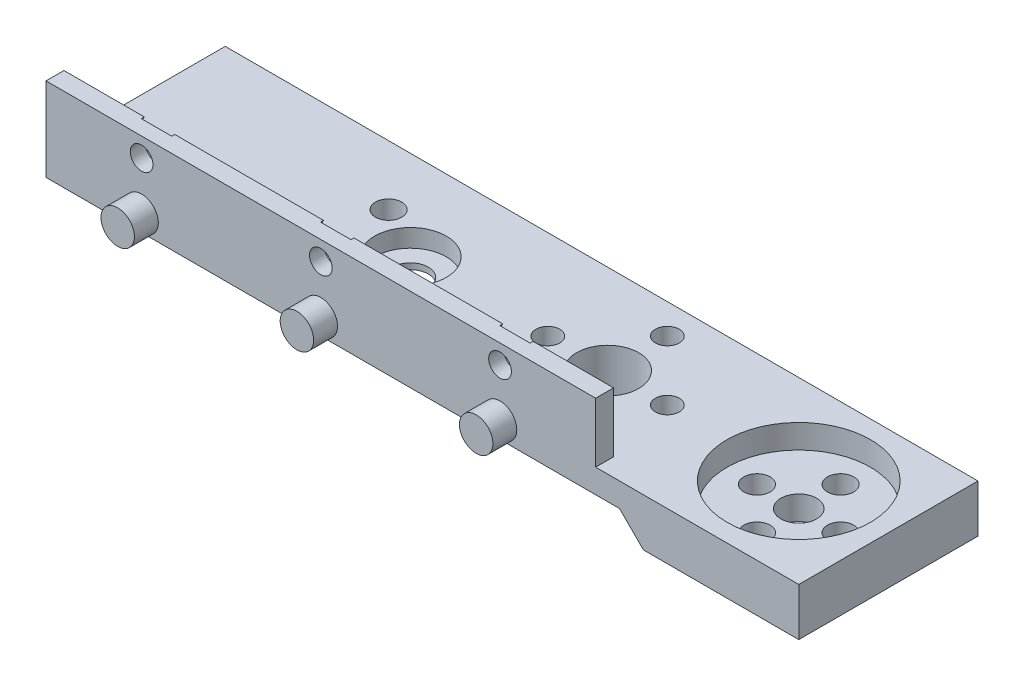
SolidWorks part; units mm, degrees
note: The reader was unsure of these and kept them because the rebuilt part matched: shared geometry of "草图2<3>", "草图1<3>", "草图1<4>", "草图1<5>", "草图1<6>".
ref_plane "前视基准面" through (0, 0, 0) normal (0, 0, 1) x (1, 0, 0)
ref_plane "上视基准面" through (0, 0, 0) normal (0, 1, 0) x (1, 0, 0)
ref_plane "右视基准面" through (0, 0, 0) normal (1, 0, 0) x (0, 0, -1)
other "Configuration Table"
sketch "草图1" plane through (0, 0, 0) normal (0, 1, 0) x (1, 0, 0)
  line L0 (-31.5, 7.5) -> (31.5, 7.5)
  line L1 (31.5, 7.5) -> (31.5, -7.5)
  line L2 (31.5, -7.5) -> (-31.5, -7.5)
  line L3 (-31.5, -7.5) -> (-31.5, 7.5)
  line L4 (-31.5, 0) -> (31.5, 0) construction
  line L5 (-12.8301, -2.5) -> (-4.1699, 2.5) construction
  line L6 (-13.3083, -5.95) -> (-3.6917, -5.95) construction
  line L7 (-13.3083, 5.95) -> (-3.6917, 5.95) construction
  line L8 (-8.5, 7.5) -> (-8.5, -7.5) construction
  line L9 (8, 0) -> (8, 4.5778) construction
  line L11 (31.5, 7.5) -> (16.5, 7.5)
  line L12 (31.5, 7.5) -> (31.5, -7.5)
  line L13 (31.5, -7.5) -> (16.5, -7.5)
  line L14 (16.5, 7.5) -> (16.5, -7.5)
  circle A0 centre (-8.5, 0) radius 1.5
  circle A1 centre (-4.1699, 2.5) radius 1.1
  circle A3 centre (-12.8301, -2.5) radius 1.1
  arc A4 (-13.3083, 5.95) -> (-13.3083, -5.95) centre (-8.5, 0) ccw construction
  circle A5 centre (8, 0) radius 2.6
  arc A6 (-3.6917, -5.95) -> (-3.6917, 5.95) centre (-8.5, 0) ccw construction
  circle A7 centre (24, 0) radius 1.5
  circle A8 centre (24, 0) radius 3.5 construction
  circle A9 centre (27.5, 0) radius 1.1
  circle A10 centre (24, -3.5) radius 1.1
  circle A11 centre (20.5, 0) radius 1.1
  circle A12 centre (24, 3.5) radius 1.1
  circle A13 centre (-12.8301, 2.5) radius 1.1
  circle A14 centre (-4.1699, -2.5) radius 1.1
  circle A15 centre (13, 0) radius 1
  circle A18 centre (3, 0) radius 1
  circle A19 centre (8, 5) radius 1
  circle A20 centre (8, -5) radius 1 [skipped]
  circle A21 centre (24, 0) radius 6
  circle A22 centre (8, 0) radius 4
  point P5 (0, 7.5)
  point P7 (-31.5, 0)
  dimension "D3" = 3
  dimension "D6" = 2.2
  dimension "D9" = 15.3
  dimension "D12" = 5.2
  dimension "D14" = 3
  dimension "D15" = 7
  dimension "D16" = 2.2
  dimension "D18" = 2
  dimension "D22" = 12
  dimension "D1" = 63
  dimension "D2" = 15
  dimension "D4" = 23
  dimension "D7" = 30
  dimension "D8" = 10
  dimension "D10" = 11.9
  dimension "D11" = 16.5
  dimension "D13" = 16
  dimension "D19" = 5
  dimension "D21" = 15
  dimension "D5" = 2
  dimension "D17" = 4
  dimension "D20" = 4
extrude "凸台-拉伸1" add sketch "草图1" along normal blind 2 contours A3 | L14 L0 L3 L2 A22 A15 A18 A19 A13 A3 A1 A0 A14 | L0 L14 L2 L1 A21 | A21 A7 A9 A10 A11 A12 | A22 A5 | A1
sketch "草图2" plane through (0, 0, 7.5) normal (0, 0, 1) x (1, 0, 0)
  line L0 (-31, 1.4) -> (31, 1.4) construction
  line L1 (-31.5, 2) -> (-31.5, 0) construction
  line L3 (31.5, 0) -> (-31.5, 0) construction
  circle A0 centre (-23.5, 1.4) radius 1.4
  circle A1 centre (-8.5, 1.4) radius 1.4
  circle A2 centre (6.5, 1.4) radius 1.4
  circle A3 centre (-23.5, 5.4) radius 0.95
  circle A4 centre (-8.5, 5.4) radius 0.95
  circle A5 centre (6.5, 5.4) radius 0.95
  line M10 (31.5, 2) -> (-31.5, 2)
  dimension "D1" = 2.8
  dimension "D2" = 2.8
  dimension "D3" = 2.8
  dimension "D8" = 1.9
  dimension "D4" = 15
  dimension "D5" = 15
  dimension "D6" = 8
  dimension "D7" = 1.4
  dimension "D9" = 4
  dimension "D10" = 3
extrude "凸台-拉伸2" add sketch "草图2" along normal blind 2 contours L0 A0 | A0 L0 M10 | A0 M10 | L0 A1 | A1 L0 M10 | A1 M10 | L0 A2 | A2 L0 M10 | A2 M10
sketch "草图3" plane through (0, 2, 0) normal (0, 1, 0) x (1, 0, 0)
  text T0 "R" font "Microsoft YaHei UI" height 3.5
sketch "草图4" plane through (0, 2, 0) normal (0, 1, 0) x (1, 0, 0)
  circle A0 centre (-8.5, 0) radius 3
  dimension "D1" = 6
extrude "切除-拉伸1" cut sketch "草图4" against normal blind 1.5
sketch "草图5" plane through (0, 2, 0) normal (0, 1, 0) x (1, 0, 0)
  line L1 (-31.5, -7.5) -> (14.5, -7.5)
  line L2 (-31.5, -7.5) -> (-31.5, -6)
  line L3 (-31.5, -6) -> (14.5, -6)
  line L4 (14.5, -7.5) -> (14.5, -6)
  dimension "D1" = 1.5
  dimension "D2" = 46
extrude "凸台-拉伸3" add sketch "草图5" along normal blind 5
extrude "切除-拉伸2" cut sketch "草图2<3>" against normal blind 6 contours A3 | A4 | A5
sketch "草图2<3>" plane through (0, 0, 7.5) normal (0, 0, 1) x (1, 0, 0) same geometry as "草图2"
sketch "草图7" plane through (0, 0, 6) normal (0, 0, -1) x (-1, 0, 0)
  line L0 (-7.597, 3.5) -> (-5.403, 3.5)
  line L1 (-5.403, 3.5) -> (-4.3061, 5.4)
  line L2 (-4.3061, 5.4) -> (-5.403, 7.3)
  line L3 (-5.403, 7.3) -> (-7.597, 7.3)
  line L4 (-7.597, 7.3) -> (-8.6939, 5.4)
  line L5 (-8.6939, 5.4) -> (-7.597, 3.5)
  line L6 (-7.597, 7.3) -> (-5.403, 3.5) construction
  line L7 (-5.403, 7.3) -> (-7.597, 3.5) construction
  line L8 (6.3061, 5.4) -> (7.403, 3.5)
  line L9 (7.403, 3.5) -> (9.597, 3.5)
  line L10 (9.597, 3.5) -> (10.6939, 5.4)
  line L11 (10.6939, 5.4) -> (9.597, 7.3)
  line L12 (9.597, 7.3) -> (7.403, 7.3)
  line L13 (7.403, 7.3) -> (6.3061, 5.4)
  line L14 (21.3061, 5.4) -> (22.403, 3.5)
  line L15 (22.403, 3.5) -> (24.597, 3.5)
  line L16 (24.597, 3.5) -> (25.6939, 5.4)
  line L17 (25.6939, 5.4) -> (24.597, 7.3)
  line L18 (24.597, 7.3) -> (22.403, 7.3)
  line L19 (22.403, 7.3) -> (21.3061, 5.4)
  line L20 (7.403, 7.3) -> (9.597, 3.5) construction
  line L21 (9.597, 7.3) -> (7.403, 3.5) construction
  circle A0 centre (-6.5, 5.4) radius 0.95
  circle A1 centre (-6.5, 5.4) radius 0.95 construction
  circle A2 centre (8.5, 5.4) radius 0.95
  circle A3 centre (8.5, 5.4) radius 0.95 construction
  point P11 (-6.5, 5.4)
  point P29 (8.5, 5.4)
  dimension "D1" = 3.8
  dimension "D2" = 3.8
  dimension "D3" = 3.8
  dimension "D4" = 120
  dimension "D5" = 120
  dimension "D6" = 120
  dimension "D7" = 3
extrude "切除-拉伸3" cut sketch "草图7" against normal blind 0.25
extrude "凸台-拉伸4" add sketch "草图1<3>" along normal blind 2 contours L0 L14 L2 L1 A21 | A21 A7 A9 A10 A11 A12
sketch "草图1<3>" plane through (0, 0, 0) normal (0, 1, 0) x (1, 0, 0) same geometry as "草图1"
extrude "凸台-拉伸5" add sketch "草图1<4>" against normal blind 2 contours L0 L14 L2 L1 A21 | A21 A7 A9 A10 A11 A12
sketch "草图1<4>" plane through (0, 0, 0) normal (0, 1, 0) x (1, 0, 0) same geometry as "草图1"
extrude "切除-拉伸4" cut sketch "草图1<5>" along normal up to surface (2 mm away) contours A21 up to face at (4.8333, 2, 2)
sketch "草图1<5>" plane through (0, 0, 0) normal (0, 1, 0) x (1, 0, 0) same geometry as "草图1"
sketch "草图8" plane through (0, 0, -7.5) normal (0, 0, -1) x (-1, 0, 0)
  line L0 (-16.5, 0) -> (-18.5, -2)
  line L1 (-16.5, -2) -> (-31.5, -2) construction
  line L2 (-18.5, -2) -> (-16.5, -2)
  line L3 (-16.5, -2) -> (-16.5, 0)
  dimension "D1" = 45
extrude "切除-拉伸5" cut sketch "草图8" against normal up to surface (15 mm away) up to face at (1.0857, 1.3, 7.5)
extrude "凸台-拉伸6" add sketch "草图1<6>" against normal blind 2 contours A22 A5
sketch "草图1<6>" plane through (0, 0, 0) normal (0, 1, 0) x (1, 0, 0) same geometry as "草图1"
